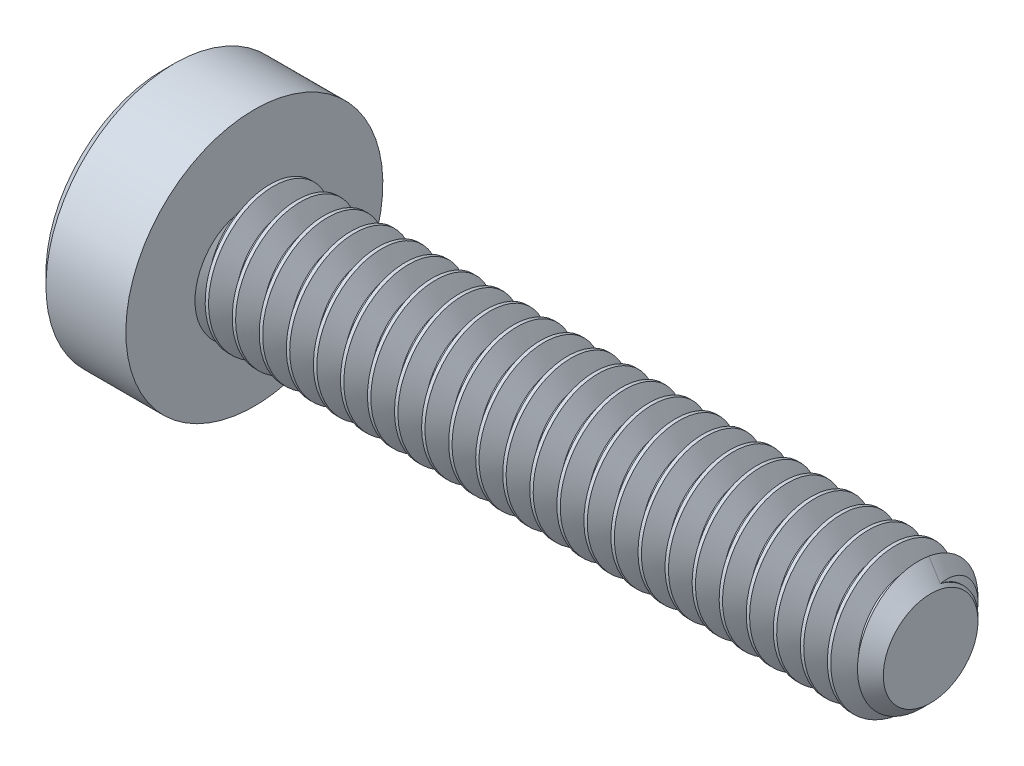
SolidWorks part; units mm, degrees
ref_plane "Front Plane" through (0, 0, 0) normal (0, 0, 1) x (1, 0, 0)
ref_plane "Top Plane" through (0, 0, 0) normal (0, 1, 0) x (1, 0, 0)
ref_plane "Right Plane" through (0, 0, 0) normal (1, 0, 0) x (0, 0, -1)
sketch "Sketch1" plane through (0, 0, 0) normal (0, 0, 1) x (1, 0, 0)
  line L0 (5, 0) -> (-5, 0) construction
  line L1 (5, 1) -> (5, -1) construction
  line L2 (-5, 1.9) -> (-5, -1.9) construction
  line L3 (-5, 1.9) -> (-6.1813, 1.9) construction
  line L4 (-6.1813, 1.9) -> (-6.35, 1.7312) construction
  line L5 (-6.35, 1.7312) -> (-6.35, -1.7313) construction
  line L6 (-6.35, -1.7313) -> (-6.1812, -1.9) construction
  line L7 (-6.1812, -1.9) -> (-5, -1.9) construction
  point P7 (-5.375, 0)
  point P12 (3.4, -1)
  dimension "D1" = 45
  dimension "D2" = 1.6
  dimension "Dec." = 2
  dimension "Length" = 10
  dimension "Head Dia" = 3.8
  dimension "Head Height" = 1.35
  dimension "Hex Depth" = 0.975
  dimension "Chamfer" = 0.1688
ref_plane "Plane1" through (5, 0, 0) normal (1, 0, 0) x (0, 0, -1)
ref_plane "Plane2" through (-6.35, 0, 0) normal (1, 0, 0) x (0, 0, -1)
sketch "Sketch2" plane through (5, 0, 0) normal (1, 0, 0) x (0, 0, -1)
  circle A0 centre (0, 0) radius 1
extrude "Boss-Extrude1" add sketch "Sketch2" against normal up to vertex (10 mm away) up to point (-5, 0, 0)
sketch "Sketch3" plane through (5, 0, 0) normal (1, 0, 0) x (0, 0, -1)
  circle A0 centre (0, 0) radius 1 construction
  circle A1 centre (0, 0) radius 1
curve "Helix/Spiral1" pitch 0.4 height 10.4 radius 1 centre (5, 0, 0) axis (-1, 0, 0) start towards (0, 1, 0) parameters "Pitch"=0.4
chamfer "Chamfer1" distance 0.3 angle 45 1 edges at (5, 0, -1)
sketch "Sketch5" plane through (0, 0, 0) normal (0, 0, 1) x (1, 0, 0)
  line L0 (4.825, 1) -> (5.175, 1)
  line L1 (5.175, 1) -> (5.025, 0.7402)
  line L2 (5.025, 0.7402) -> (4.975, 0.7402)
  line L3 (4.975, 0.7402) -> (4.825, 1)
  line L4 (5, 0.7402) -> (5, 1) construction
  line L5 (4.9, 0.8701) -> (5.1, 0.8701) construction
  dimension "D1" = 60
  dimension "D2" = 0.2
  dimension "D3" = 0.05
sweep "Cut-Sweep1" cut profiles "Sketch5" path "Helix/Spiral1"
sketch "Sketch4" plane through (-6.35, 0, 0) normal (1, 0, 0) x (0, 0, -1)
  line L0 (-1.9, 0.7937) -> (1.9, 0.7937) construction
  line L1 (0, 0.7506) -> (-0.65, 0.3753)
  line L2 (-0.65, 0.3753) -> (-0.65, -0.3753)
  line L3 (-0.65, -0.3753) -> (0, -0.7506)
  line L4 (0, -0.7506) -> (0.65, -0.3753)
  line L5 (0.65, -0.3753) -> (0.65, 0.3753)
  line L6 (0.65, 0.3753) -> (0, 0.7506)
  line L7 (0, 0) -> (0, 0.7937) construction
  circle A0 centre (0, 0) radius 0.65 construction
  dimension "D1" = 3.8
  dimension "Hex Size" = 1.3
  dimension "D2" = 0.7937
sketch "Sketch6" plane through (0, 0, 0) normal (0, 0, 1) x (1, 0, 0)
  line L0 (-6.1813, 1.9) -> (-6.35, 1.7312) construction
  line L1 (-5, 1.9) -> (-6.1813, 1.9) construction
  line L2 (-5, 1.9) -> (-5, -1.9) construction
  line L3 (-6.35, 1.7312) -> (-6.35, -1.7313) construction
  line L4 (-6.1813, 1.9) -> (-6.35, 1.7312)
  line L5 (-5, 1.9) -> (-6.1813, 1.9)
  line L6 (-5, 1.9) -> (-5, 0)
  line L7 (-6.35, 1.7312) -> (-6.35, 0)
  line L8 (-5, 0) -> (-6.35, 0) construction
  line L9 (-5, 0) -> (-6.35, 0)
revolve "Revolve1" add sketch "Sketch6" angle 360 about L8
extrude "Cut-Extrude1" cut sketch "Sketch4" along normal up to vertex (0.975 mm away) up to point (-5.375, 0, 0)
sketch "Sketch8" plane through (-6.35, 0, 0) normal (-1, 0, 0) x (0, 0, 1)
  circle A1 centre (0, 0) radius 0.7506
extrude "Cut-Extrude2" cut sketch "Sketch8" against normal through all draft 45
equation "\"D3@Helix/Spiral1\" = \"Length@Sketch1\"+\"Pitch@Helix/Spiral1\""
equation "\"D3@Sketch5\" = \"Pitch@Helix/Spiral1\"*.125"
equation "\"D2@Sketch5\" = \"Pitch@Helix/Spiral1\"*.50"
equation "\"D1@Chamfer1\" = \"Pitch@Helix/Spiral1\"*.75"
equation "\"D2@Sketch1\" = \"Pitch@Helix/Spiral1\"*4"
equation "\"D1@Sketch4\" = \"Head Dia@Sketch1\""
equation "\"Chamfer@Sketch1\" = \"Head Height@Sketch1\"/8"
